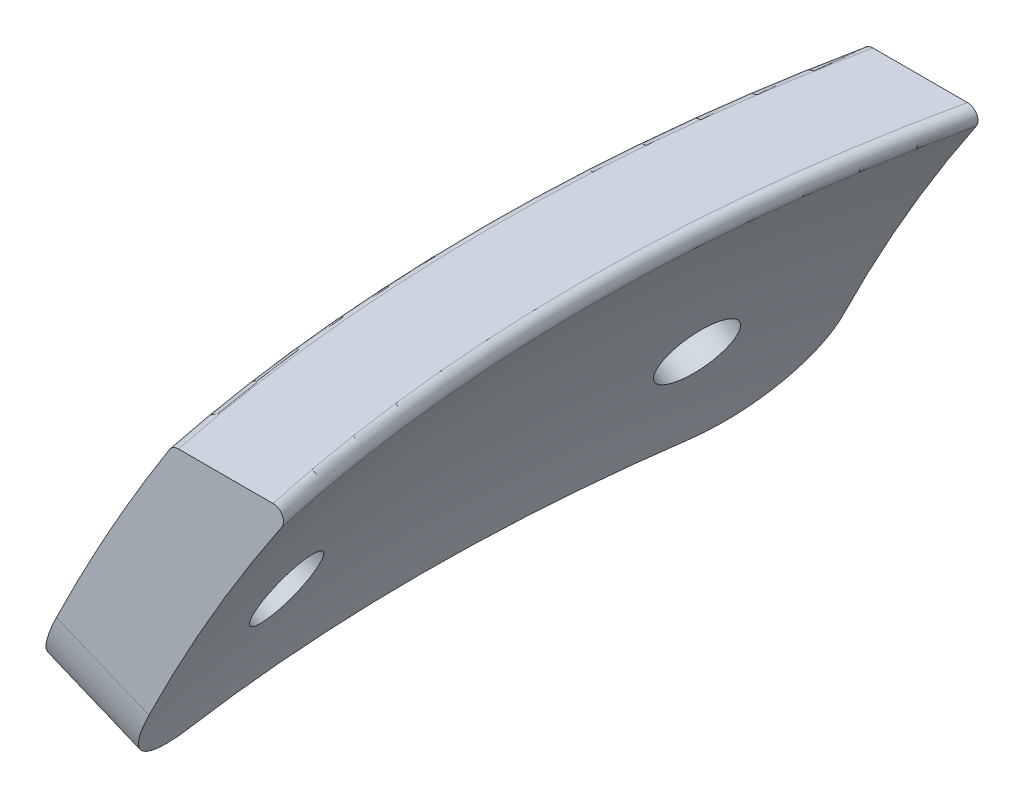
SolidWorks part; units mm, degrees
material "Polyether Polyol"
ref_plane "Front Plane" through (0, 0, 0) normal (0, 0, 1) x (1, 0, 0)
ref_plane "Top Plane" through (0, 0, 0) normal (0, 1, 0) x (1, 0, 0)
ref_plane "Right Plane" through (0, 0, 0) normal (1, 0, 0) x (0, 0, -1)
sketch "Sketch1" plane through (0, 0, 0) normal (0, 0, 1) x (1, 0, 0)
  line L2 (-166.6461, 194.6685) -> (-145.5262, 194.6685) construction
  line L3 (-181.5068, 166.0796) -> (-172.7242, 162.3929) construction
  line L6 (-166.6461, 194.6685) -> (-155.2793, 194.6685)
  line L7 (-181.5068, 166.0796) -> (-172.7242, 162.3929)
  line L8 (0, 0) -> (0, 244.1177) construction
  arc A0 (-166.6461, 194.6685) -> (-181.5068, 166.0796) centre (0, 89.8878) ccw construction
  arc A1 (-161.2979, 185.1435) -> (-172.7242, 162.3929) centre (0, 89.8878) ccw construction
  arc A2 (-166.6461, 194.6685) -> (-181.5068, 166.0796) centre (0, 89.8878) ccw
  arc A3 (-161.2979, 185.1435) -> (-172.7242, 162.3929) centre (0, 89.8878) ccw
  arc A4 (-161.2979, 185.1435) -> (-155.2793, 194.6685) centre (0, 89.8878) cw
revolve "Revolve1" add sketch "Sketch1" angle 25 mid plane about L8
sketch "Sketch2" plane through (0, 0, 0) normal (0, 0, 1) x (1, 0, 0)
  line L0 (0, 89.8878) -> (-166.9078, 174.9315) construction
  line L1 (0, 0) -> (0, 244.1177) construction
  arc A1 (-161.2979, 185.1435) -> (-172.7242, 162.3929) centre (0, 89.8878) ccw construction
  dimension "D1" = 63
ref_plane "Plane1" through (36.3604, 71.3612, 0) normal (0.454, 0.891, 0) x (-0.891, 0.454, 0)
sketch "Sketch4" plane through (36.3604, 71.3612, 0) normal (0.454, 0.891, 0) x (-0.891, 0.454, 0)
  line L0 (219.8801, 19.237) -> (239.1484, 20.9228) construction
  line L1 (219.5688, 22.7953) -> (238.8371, 24.4811)
  line L2 (219.5688, 22.7953) -> (219.8801, 19.237)
  line L3 (40.8082, 0) -> (228.1332, 0) construction
  line L4 (219.8801, 19.237) -> (239.1484, 20.9228)
  line L5 (238.8371, 24.4811) -> (239.1484, 20.9228)
  dimension "D1" = 7.1437
  dimension "D2" = 5
revolve "Cut-Revolve1" cut sketch "Sketch4" angle 360 about L0
mirror "Mirror1" about plane through (0, 0, 0) normal (0, 0, 1) of "Cut-Revolve1"
sketch "Sketch5" plane through (0, 0, 0) normal (0, 1, 0) x (1, 0, 0)
  line L1 (-151.5985, 33.6086) -> (-201.5408, 33.6086)
  line L2 (-151.5985, 33.6086) -> (-151.5985, -33.6086)
  line L3 (-151.5985, -33.6086) -> (-201.5408, -33.6086)
  line L4 (-201.5408, 33.6086) -> (-201.5408, -33.6086)
extrude "Cut-Extrude2" cut sketch "Sketch5" along normal through all flip side to cut
fillet "Fillet1" radius 10 2 edges
fillet "Fillet2" radius 1 2 edges at (-166.6461, 194.6685, 0) (-155.2793, 194.6685, 0)
